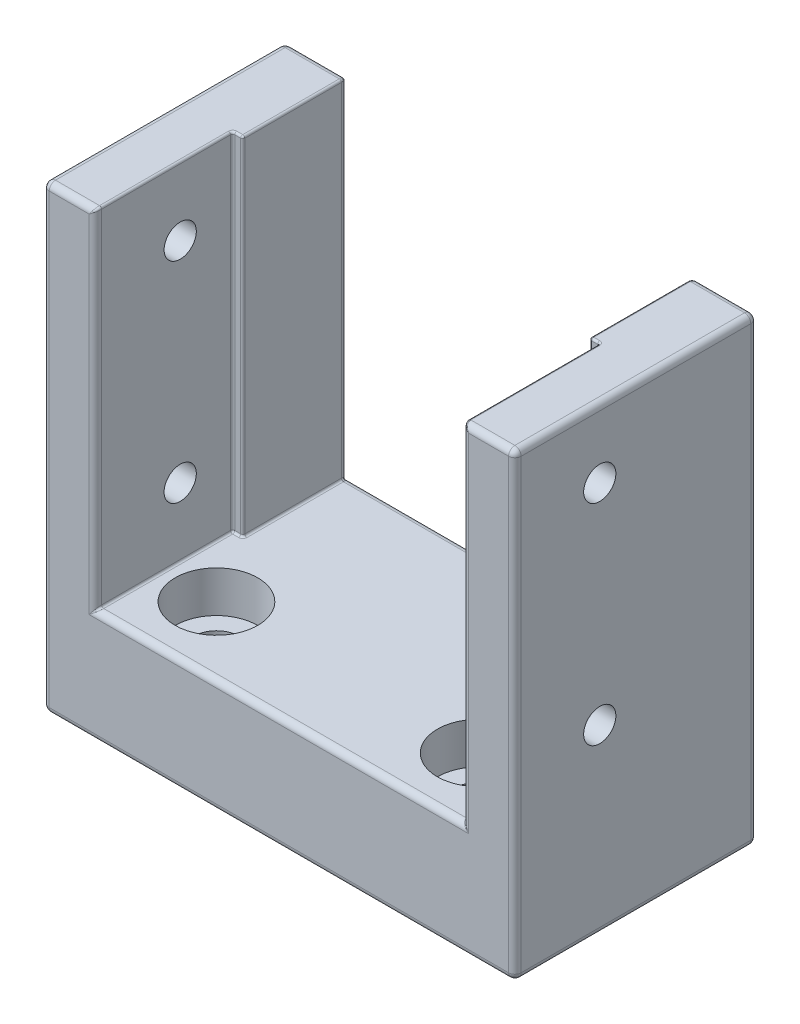
SolidWorks part; units mm, degrees
material "PLA"
ref_plane "Front Plane" through (0, 0, 0) normal (0, 0, 1) x (1, 0, 0)
ref_plane "Top Plane" through (0, 0, 0) normal (0, 1, 0) x (1, 0, 0)
ref_plane "Right Plane" through (0, 0, 0) normal (1, 0, 0) x (0, 0, -1)
sketch "Sketch1" plane through (0, 0, 0) normal (0, 1, 0) x (1, 0, 0)
  line L1 (-22.225, 14.6625) -> (22.225, 14.6625)
  line L2 (-22.225, 14.6625) -> (-22.225, -14.6625)
  line L3 (-22.225, -14.6625) -> (22.225, -14.6625)
  line L4 (22.225, 14.6625) -> (22.225, -14.6625)
  point P4 (0, -14.6625)
  point P6 (-22.225, 0)
  dimension "D1" = 29.325
  dimension "D2" = 44.45
extrude "Boss-Extrude1" add sketch "Sketch1" against normal blind 13.685
sketch "Sketch2" plane through (22.225, 0, 0) normal (1, 0, 0) x (0, 0, -1)
  line L0 (14.6625, -13.685) -> (14.6625, 0) construction
  line L1 (-14.6625, -13.685) -> (14.6625, -13.685)
  line L2 (-14.6625, -13.685) -> (-14.6625, 42)
  line L3 (-14.6625, 42) -> (14.6625, 42)
  line L4 (14.6625, -13.685) -> (14.6625, 42)
  point P5 (25.7497, -4.16)
  point P6 (25.7497, -29.56)
  dimension "D1" = 55.685
extrude "Boss-Extrude2" add sketch "Sketch2" along normal blind 6.35
hole_wizard "M3.5 Clearance Hole1" positions "Sketch5" profile "Sketch6" hole size "M3.5" standard "ANSI Metric" end condition through all
sketch "Sketch5" plane through (28.575, 0, 0) normal (1, 0, 0) x (0, 0, -1)
  line L1 (14.6625, 42) -> (-14.6625, 42) construction
  line L2 (-14.6625, 42) -> (-14.6625, -13.685) construction
  point P0 (-4.3875, 33.7)
  point P2 (-4.3875, 8.3)
  dimension "D1" = 10.275
  dimension "D2" = 8.3
  dimension "D3" = 25.4
sketch "Sketch6" plane through (28.575, 33.7, 4.3875) normal (0, 1, 0) x (0, 0, -1)
  line L0 (0, 0) -> (0, 50.8)
  line L1 (0, 50.8) -> (1.95, 50.8)
  line L2 (1.95, 50.8) -> (1.95, 0)
  line L5 (1.95, 0) -> (0, 0)
  line L11 (0, -6.35) -> (0, 107.95) construction
  dimension "Thru Hole Dia." = 3.9
  dimension "Thru Hole Depth" = 50.8
mirror "Mirror1" about plane through (0, 0, 0) normal (1, 0, 0) of "Boss-Extrude2", "M3.5 Clearance Hole1"
sketch "Sketch8" plane through (22.225, 0, 0) normal (-1, 0, 0) x (0, 0, 1)
  line L0 (-14.6625, 42) -> (14.6625, 42) construction
  line L1 (-14.6625, 0) -> (-1.9625, 0)
  line L2 (-14.6625, 0) -> (-14.6625, 42)
  line L3 (-14.6625, 42) -> (-1.9625, 42)
  line L4 (-1.9625, 0) -> (-1.9625, 42)
  dimension "D1" = 12.7
extrude "Boss-Extrude6" add sketch "Sketch8" along normal blind 1.225
mirror "Mirror2" about plane through (0, 0, 0) normal (1, 0, 0) of "Boss-Extrude6"
hole_wizard "CBORE for M5 SHCS1" positions "Sketch9" profile "Sketch10" counterbore size "M5" standard "ANSI Metric" end condition through all
sketch "Sketch9" plane through (0, 0, 0) normal (0, 1, 0) x (1, 0, 0)
  line L0 (-22.225, 1.9625) -> (-22.225, -14.6625) construction
  line L1 (0, -16.1288) -> (0, 16.1288) construction
  point P0 (15.875, -6.35)
  point P2 (-15.875, -6.35)
  point P8 (-22.225, -6.35)
  dimension "D1" = 15.875
  dimension "D2" = 15.875
sketch "Sketch10" plane through (15.875, 0, 6.35) normal (1, 0, 0) x (0, 0, 1)
  line L0 (0, 0) -> (0, 13.685)
  line L1 (0, 13.685) -> (2.75, 13.685)
  line L3 (2.75, 13.685) -> (2.75, 5)
  line L4 (2.75, 5) -> (5, 5)
  line L5 (5, 5) -> (5, 0)
  line L7 (5, 0) -> (0, 0)
  line L11 (0, -6.35) -> (0, 107.95) construction
  dimension "Thru Hole Dia." = 5.5
  dimension "Thru Hole Depth" = 13.685
  dimension "C'Bore Dia." = 10
  dimension "C'Bore Depth" = 5
fillet "Fillet1" radius 0.762 22 edges at (-21, 21, -14.6625) (-24.7875, 42, -14.6625) (-28.575, 14.1575, -14.6625) (28.575, 14.1575, -14.6625) (24.7875, 42, -14.6625) (21, 21, -14.6625) (0, 0, -14.6625) (22.225, 21, 14.6625) (25.4, 42, 14.6625) (28.575, 14.1575, 14.6625) (-28.575, 14.1575, 14.6625) (-25.4, 42, 14.6625) (-22.225, 21, 14.6625) (0, 0, 14.6625) (28.575, -13.685, 0) (0, -13.685, -14.6625) (-28.575, -13.685, 0) (0, -13.685, 14.6625) (-15.875, -13.685, 9.1) (15.875, -13.685, 9.1) (28.575, 42, 0) (-28.575, 42, 0)
fillet "Fillet2" radius 0.254 24 edges at (-21.2232, -0.2232, -14.4393) (21.2232, -0.2232, -14.4393) (22.4482, 41.7768, 14.4393) (-21, 0, -7.9315) (21, 0, -7.9315) (22.225, 42, 5.969) (-22.4482, -0.2232, 14.4393) (-21.2232, 41.7768, -14.4393) (-22.4482, 41.7768, 14.4393) (22.4482, -0.2232, 14.4393) (21.2232, 41.7768, -14.4393) (-22.225, 0, 5.969) (-21.6125, 0, -1.9625) (-21, 42, -7.9315) (-21, 21, -1.9625) (-22.225, 21, -1.9625) (-21.6125, 42, -1.9625) (-22.225, 42, 5.969) (21.6125, 0, -1.9625) (22.225, 0, 5.969) (21.6125, 42, -1.9625) (21, 21, -1.9625) (22.225, 21, -1.9625) (21, 42, -7.9315)
